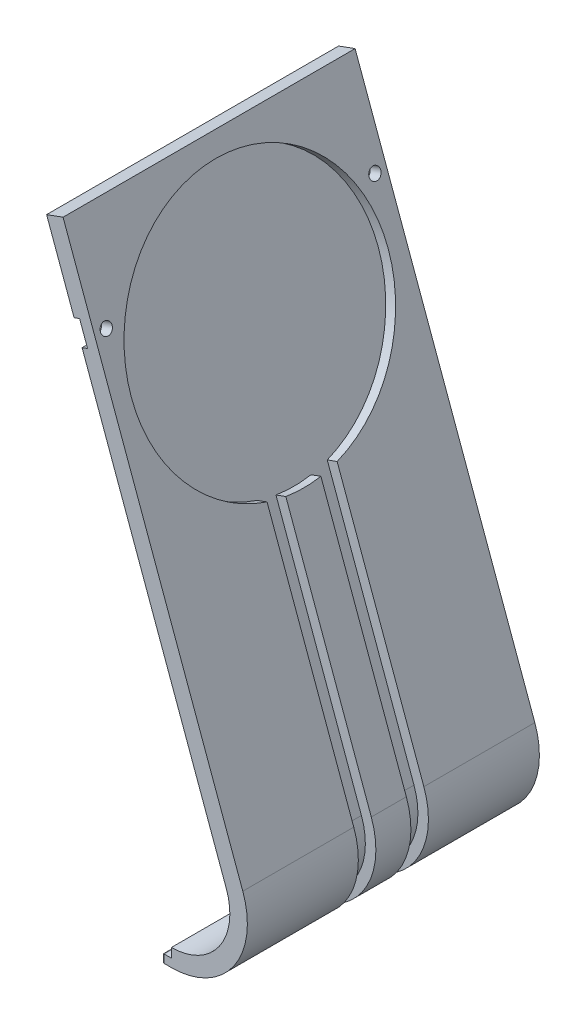
SolidWorks part; units mm, degrees
material "PLA"
ref_plane "前视基准面" through (0, 0, 0) normal (0, 0, 1) x (1, 0, 0)
ref_plane "上视基准面" through (0, 0, 0) normal (0, 1, 0) x (1, 0, 0)
ref_plane "右视基准面" through (0, 0, 0) normal (1, 0, 0) x (0, 0, -1)
other "Configuration Table"
sketch "草图2" plane through (0, 0, 0) normal (0, 0, 1) x (1, 0, 0)
  line L0 (38.2711, 18.4699) -> (5.8755, 107.4762) construction
  line L5 (38.2711, 18.4699) -> (7.4967, 103.022)
  line L10 (28.8742, 5.0497) -> (28.8742, 4.0497) construction
  line L11 (6.4731, 108.7579) -> (8.8224, 109.6129) construction
  arc A0 (28.8742, 5.0497) -> (38.2711, 18.4699) centre (28.8742, 15.0497) ccw
  arc A1 (28.8742, 5.0497) -> (38.2711, 18.4699) centre (28.8742, 15.0497) ccw construction
  dimension "D2" = 10
  dimension "D1" = 5.74
extrude "整体拉伸-薄壁1" add sketch "草图2" along normal mid plane 50 thin thin type one direction wall 3
sketch "草图4" plane through (42.5494, 15.4867, 0) normal (0.9397, 0.342, 0) x (0, 0, -1)
  line L0 (-25, 94.245) -> (25, 94.245) construction
  circle A0 centre (0, 68.845) radius 22
  dimension "D1" = 44
  dimension "D2" = 25.4
extrude "中间圆切除-拉伸1" cut sketch "草图4" against normal blind 1.8
sketch "草图3" plane through (0, 0, 0) normal (0, 0, 1) x (1, 0, 0)
  line L0 (41.0902, 19.4959) -> (10.3157, 104.0481) construction
  line L1 (41.0902, 19.4959) -> (10.3157, 104.0481) construction
  line L2 (28.8742, 2.0497) -> (28.8742, 5.0497) construction
  line L5 (39.3988, 18.8803) -> (24.836, 58.891)
  line L6 (39.3988, 18.8803) -> (8.6243, 103.4325) construction
  line L7 (28.8742, 3.8497) -> (28.8742, 3.8497) construction
  line L9 (24.836, 58.891) -> (26.5275, 59.5067) construction
  line L16 (24.836, 58.891) -> (23.81, 61.7101)
  line L17 (27.0769, 3.9492) -> (17.8463, 8.166) construction
  arc A0 (28.8742, 5.0497) -> (38.2711, 18.4699) centre (28.8742, 15.0497) ccw construction
  arc A1 (17.8463, 8.166) -> (41.0902, 19.4959) centre (28.8742, 15.0497) ccw construction
  arc A2 (28.8742, 3.8497) -> (39.3988, 18.8803) centre (28.8742, 15.0497) ccw
  dimension "D2" = 3
  dimension "D1" = 1.8
extrude "线槽切除-拉伸-薄壁1" cut sketch "草图3" against normal blind 3 from offset 6 thin thin type one direction wall 1.8
mirror "镜向1" about plane through (0, 0, 0) normal (0, 0, 1) of "线槽切除-拉伸-薄壁1"
sketch "草图11" plane through (28.8742, 0, 0) normal (-1, 0, 0) x (0, 0, 1)
  line L0 (-25, 2.0497) -> (-25, 5.0497) construction
  line L1 (-25, 3.4497) -> (-6.1, 3.4497)
  line L2 (-25, 3.4497) -> (-25, 2.0497)
  line L3 (-25, 2.0497) -> (-6.1, 2.0497)
  line L4 (-6.1, 3.4497) -> (-6.1, 2.0497)
  line L5 (25, 2.0497) -> (6, 2.0497) construction
  line L6 (6.1, 3.4497) -> (25, 3.4497)
  line L7 (6.1, 3.4497) -> (6.1, 2.0497)
  line L8 (6.1, 2.0497) -> (25, 2.0497)
  line L9 (25, 3.4497) -> (25, 2.0497)
  line L11 (-6, 2.0497) -> (-6, 3.8497) construction
  line L13 (6, 2.0497) -> (6, 3.8497) construction
  line L14 (25, 5.0497) -> (-25, 5.0497) construction
  dimension "D1" = 1.6
  dimension "D2" = 0.1
  dimension "D3" = 0.1
  dimension "D4" = 1.6
extrude "底部卡扣凸台-拉伸3" add sketch "草图11" along normal blind 1.5
fillet "底部卡扣圆角1" radius 0.25 8 edges at (27.3742, 3.4497, 15.55) (27.3742, 2.7497, 25) (27.3742, 2.0497, 15.55) (27.3742, 2.7497, 6.1) (27.3742, 3.4497, -15.55) (27.3742, 2.7497, -6.1) (27.3742, 2.0497, -15.55) (27.3742, 2.7497, -25)
sketch "草图12" plane through (39.7304, 14.4607, 0) normal (-0.9397, -0.342, 0) x (0, 0, 1)
  line L0 (-36.5, 80.4828) -> (36.5, 80.4828) construction
  line L2 (-25, 4.2665) -> (-25, 94.245) construction
  line L3 (25, 4.2665) -> (25, 94.245) construction
  circle A0 centre (23, 78.4828) radius 1
  circle A1 centre (-23, 78.4828) radius 1
  dimension "D1" = 2
  dimension "D2" = 2
  dimension "D3" = 2
  dimension "D4" = 2
  dimension "D5" = 2
  dimension "D6" = 2
extrude "螺丝孔" cut sketch "草图12" against normal through all
sketch "草图13" plane through (39.7304, 14.4607, 0) normal (-0.9397, -0.342, 0) x (0, 0, 1)
  line L0 (25, 4.2665) -> (25, 94.245) construction
  line L1 (23, 80.4828) -> (25, 80.4828)
  line L3 (23, 76.4828) -> (25, 76.4828)
  line L4 (25, 80.4828) -> (25, 76.4828)
  line L5 (-36.5, 80.4828) -> (36.5, 80.4828) construction
  line L6 (0, 94.245) -> (0, 78.3622) construction
  line L7 (25, 94.245) -> (-25, 94.245) construction
  line L8 (-25, 80.4828) -> (-25, 76.4828)
  line L9 (-23, 76.4828) -> (-25, 76.4828)
  line L10 (-23, 80.4828) -> (-25, 80.4828)
  arc A0 (23, 80.4828) -> (23, 76.4828) centre (23, 78.4828) ccw
  arc A1 (-23, 80.4828) -> (-23, 76.4828) centre (-23, 78.4828) cw
  dimension "D1" = 4
extrude "切除-拉伸1" cut sketch "草图13" against normal blind 1
